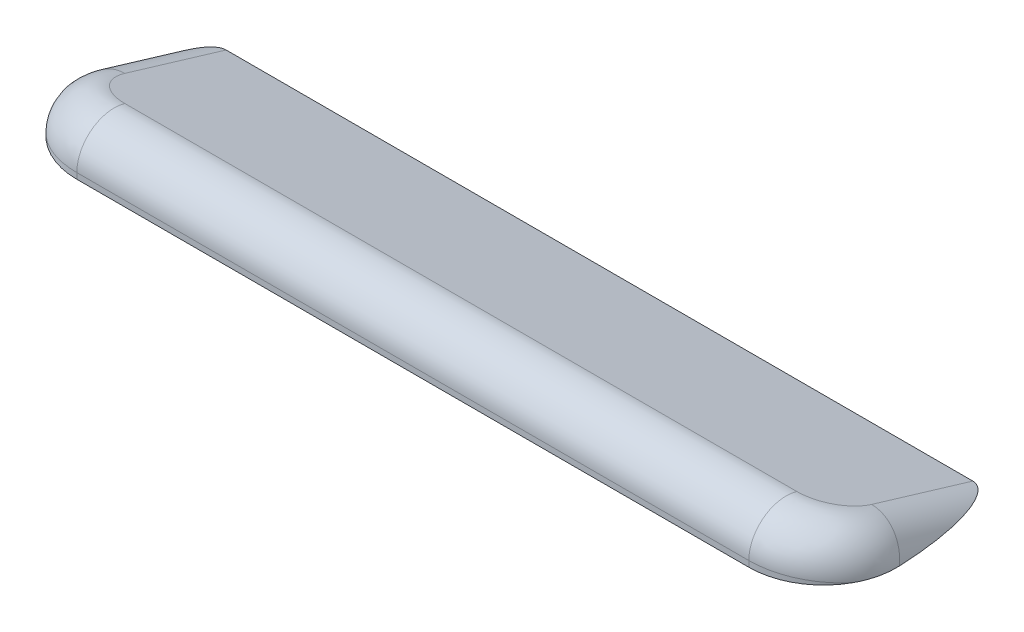
SolidWorks part; units mm, degrees
ref_plane "前视基准面" through (0, 0, 0) normal (0, 0, 1) x (1, 0, 0)
ref_plane "上视基准面" through (0, 0, 0) normal (0, 1, 0) x (1, 0, 0)
ref_plane "右视基准面" through (0, 0, 0) normal (1, 0, 0) x (0, 0, -1)
other "Configuration Table"
sketch "草图1" plane through (0, 0, 0) normal (1, 0, 0) x (0, 0, -1)
  line L0 (0, 0) -> (25, 0)
  line L1 (25, 0) -> (0, 7.5)
  line L2 (0, 7.5) -> (0, 0)
  dimension "D1" = 25
  dimension "D2" = 7.5
extrude "凸台-拉伸1" add sketch "草图1" along normal blind 110
fillet "圆角1" radius 10 2 edges at (0, 3.75, 0) (110, 3.75, 0)
fillet "圆角2" radius 5 5 edges at (110, 2.25, -17.5) (107.0711, 6.6213, -2.9289) (0, 2.25, -17.5) (2.9289, 6.6213, -2.9289) (55, 7.5, 0)
